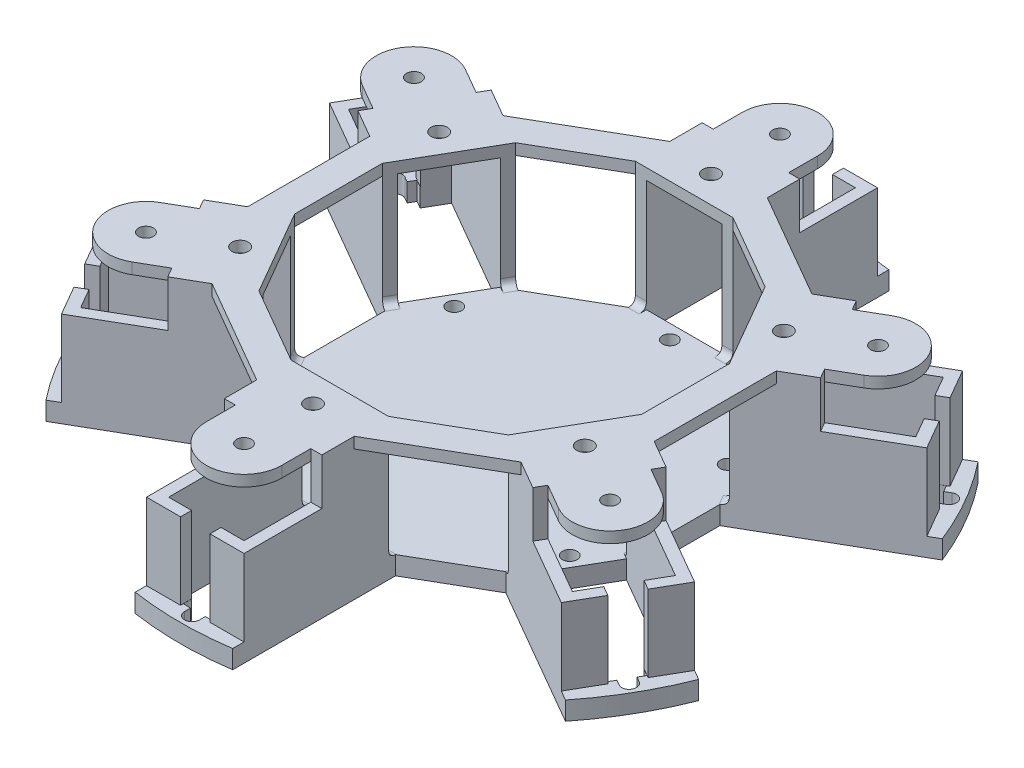
SolidWorks part; units mm, degrees
material "ABS"
ref_plane "Front" through (0, 0, 0) normal (0, 0, 1) x (1, 0, 0)
ref_plane "Top" through (0, 0, 0) normal (0, 1, 0) x (1, 0, 0)
ref_plane "Right" through (0, 0, 0) normal (1, 0, 0) x (0, 0, -1)
sketch "Sketch1" plane through (0, 0, 0) normal (0, 1, 0) x (1, 0, 0)
  line L0 (0, -57.15) -> (0, -56.41) construction
  line L1 (0, 57.15) -> (-49.4934, 28.575) construction
  line L2 (-49.4934, 28.575) -> (-49.4934, -28.575) construction
  line L3 (-49.4934, -28.575) -> (0, -57.15) construction
  line L4 (0, -57.15) -> (49.4934, -28.575) construction
  line L5 (49.4934, -28.575) -> (49.4934, 28.575) construction
  line L6 (49.4934, 28.575) -> (0, 57.15) construction
  line L7 (42.3635, 31.9642) -> (22.445, 20.4642)
  line L8 (-6.5, 52.67) -> (-2.5207, 52.67)
  line L9 (-6.5, 52.67) -> (-6.5, 29.67)
  line L10 (-6.5, 29.67) -> (6.5, 29.67)
  line L11 (6.5, 52.67) -> (6.5, 29.67)
  line L12 (-6.5, 52.67) -> (6.5, 29.67) construction
  line L13 (-6.5, 29.67) -> (6.5, 52.67) construction
  line L14 (42.3635, 31.9642) -> (44.3532, 28.518)
  line L15 (48.8635, 20.7058) -> (28.945, 9.2058)
  line L16 (22.445, 20.4642) -> (28.945, 9.2058)
  line L17 (48.8635, -20.7058) -> (28.945, -9.2058)
  line L18 (48.8635, -20.7058) -> (46.8739, -24.152)
  line L19 (42.3635, -31.9642) -> (22.445, -20.4642)
  line L20 (28.945, -9.2058) -> (22.445, -20.4642)
  line L21 (6.5, -52.67) -> (6.5, -29.67)
  line L22 (6.5, -52.67) -> (2.5207, -52.67)
  line L23 (-6.5, -52.67) -> (-6.5, -29.67)
  line L24 (6.5, -29.67) -> (-6.5, -29.67)
  line L25 (-42.3635, -31.9642) -> (-22.445, -20.4642)
  line L26 (-42.3635, -31.9642) -> (-44.3532, -28.518)
  line L27 (-48.8635, -20.7058) -> (-28.945, -9.2058)
  line L28 (-22.445, -20.4642) -> (-28.945, -9.2058)
  line L29 (-48.8635, 20.7058) -> (-28.945, 9.2058)
  line L30 (-48.8635, 20.7058) -> (-46.8739, 24.152)
  line L31 (-42.3635, 31.9642) -> (-22.445, 20.4642)
  line L32 (-28.945, 9.2058) -> (-22.445, 20.4642)
  line L33 (-1.27, 55.14) -> (-1.27, 54.1138)
  line L34 (-1.27, 54.1138) -> (-2.5207, 54.1138)
  line L35 (-2.5207, 54.1138) -> (-2.5207, 52.67)
  line L37 (2.5207, 54.1138) -> (2.5207, 52.67)
  line L38 (1.27, 54.1138) -> (2.5207, 54.1138)
  line L39 (1.27, 55.14) -> (1.27, 54.1138)
  line L40 (0, 53.87) -> (0, 57.15) construction
  line L41 (47.1176, 28.6698) -> (46.2289, 28.1567)
  line L42 (46.2289, 28.1567) -> (45.6035, 29.2399)
  line L43 (45.6035, 29.2399) -> (44.3532, 28.518)
  line L45 (48.1242, 24.8739) -> (46.8739, 24.152)
  line L46 (47.4989, 25.957) -> (48.1242, 24.8739)
  line L47 (48.3876, 26.4701) -> (47.4989, 25.957)
  line L48 (48.3876, -26.4701) -> (47.4989, -25.957)
  line L49 (47.4989, -25.957) -> (48.1242, -24.8739)
  line L50 (48.1242, -24.8739) -> (46.8739, -24.152)
  line L52 (45.6035, -29.2399) -> (44.3532, -28.518)
  line L53 (46.2289, -28.1567) -> (45.6035, -29.2399)
  line L54 (47.1176, -28.6698) -> (46.2289, -28.1567)
  line L55 (1.27, -55.14) -> (1.27, -54.1138)
  line L56 (1.27, -54.1138) -> (2.5207, -54.1138)
  line L57 (2.5207, -54.1138) -> (2.5207, -52.67)
  line L59 (-2.5207, -54.1138) -> (-2.5207, -52.67)
  line L60 (-1.27, -54.1138) -> (-2.5207, -54.1138)
  line L61 (-1.27, -55.14) -> (-1.27, -54.1138)
  line L62 (-47.1176, -28.6698) -> (-46.2289, -28.1567)
  line L63 (-46.2289, -28.1567) -> (-45.6035, -29.2399)
  line L64 (-45.6035, -29.2399) -> (-44.3532, -28.518)
  line L66 (-48.1242, -24.8739) -> (-46.8739, -24.152)
  line L67 (-47.4989, -25.957) -> (-48.1242, -24.8739)
  line L68 (-48.3876, -26.4701) -> (-47.4989, -25.957)
  line L69 (-48.3876, 26.4701) -> (-47.4989, 25.957)
  line L70 (-47.4989, 25.957) -> (-48.1242, 24.8739)
  line L71 (-48.1242, 24.8739) -> (-46.8739, 24.152)
  line L73 (-45.6035, 29.2399) -> (-44.3532, 28.518)
  line L74 (-46.2289, 28.1567) -> (-45.6035, 29.2399)
  line L75 (-47.1176, 28.6698) -> (-46.2289, 28.1567)
  line L76 (2.5207, 52.67) -> (6.5, 52.67)
  line L77 (-44.3532, 28.518) -> (-42.3635, 31.9642)
  line L78 (-46.8739, -24.152) -> (-48.8635, -20.7058)
  line L79 (0, -52.67) -> (0, 49.4934) construction
  line L80 (-2.5207, -52.67) -> (-6.5, -52.67)
  line L81 (44.3532, -28.518) -> (42.3635, -31.9642)
  line L82 (46.8739, 24.152) -> (48.8635, 20.7058)
  circle A0 centre (0, 0) radius 57.15
  circle A1 centre (0, 0) radius 49.4934 construction
  arc A2 (1.27, 55.14) -> (-1.27, 55.14) centre (0, 55.14) ccw
  circle A3 centre (0, 27.2) radius 1.27
  circle A5 centre (23.5559, 13.6) radius 1.27
  circle A7 centre (23.5559, -13.6) radius 1.27
  circle A9 centre (0, -27.2) radius 1.27
  circle A11 centre (-23.5559, -13.6) radius 1.27
  circle A13 centre (-23.5559, 13.6) radius 1.27
  circle A14 centre (-47.7526, 27.57) radius 1.27 [skipped]
  circle A15 centre (-47.7526, -27.57) radius 1.27 [skipped]
  circle A16 centre (0, -55.14) radius 1.27 [skipped]
  circle A17 centre (47.7526, -27.57) radius 1.27 [skipped]
  circle A18 centre (47.7526, 27.57) radius 1.27 [skipped]
  arc A19 (48.3876, 26.4701) -> (47.1176, 28.6698) centre (47.7526, 27.57) ccw
  arc A20 (47.1176, -28.6698) -> (48.3876, -26.4701) centre (47.7526, -27.57) ccw
  arc A21 (-1.27, -55.14) -> (1.27, -55.14) centre (0, -55.14) ccw
  arc A22 (-48.3876, -26.4701) -> (-47.1176, -28.6698) centre (-47.7526, -27.57) ccw
  arc A23 (-47.1176, 28.6698) -> (-48.3876, 26.4701) centre (-47.7526, 27.57) ccw
  point P3 (0, 41.17)
  point P11 (0, 0)
  point P13 (0, 0)
  point P14 (0, 0)
  point P64 (0, 0)
  point P69 (0, 52.67)
  point P120 (0, 0)
  dimension "D1" = 114.3
  dimension "D4" = 2.54
  dimension "D5" = 2.54
  dimension "D2" = 23
  dimension "D3" = 13
  dimension "D6" = 27.94
  dimension "D7" = 13.97
  dimension "D9" = 6
  dimension "D8" = 6
extrude "Boss-Extrude2" add sketch "Sketch1" along normal blind 3.175
sketch "Sketch2" plane through (0, 3.175, 0) normal (0, 1, 0) x (1, 0, 0)
  line L0 (0, 0) -> (-8.405, 56.5286) construction
  line L1 (0, 0) -> (-44.7527, 35.5432) construction
  line L2 (0, 0) -> (-25.4, 43.9941) construction
  line L3 (-44.7527, 35.5432) -> (-8.405, 56.5286) construction
  line L4 (-22.445, 20.4642) -> (-6.5, 29.67) construction
  line L6 (-8.405, 28.4804) -> (-20.4623, 21.5192)
  line L7 (-20.4623, 21.5192) -> (-44.7527, 35.5432)
  line L8 (-22.445, 20.4642) -> (-42.3635, 31.9642) construction
  line L9 (-8.405, 28.4804) -> (-8.405, 56.5286)
  line L25 (-6.5, 52.67) -> (-6.5, 29.67) construction
  line L26 (8.405, 28.4804) -> (8.405, 56.5286)
  line L27 (20.4623, 21.5192) -> (8.405, 28.4804)
  line L28 (20.4623, 21.5192) -> (44.7527, 35.5432)
  line L29 (28.8673, 6.9613) -> (53.1577, 20.9853)
  line L30 (28.8673, -6.9613) -> (28.8673, 6.9613)
  line L31 (28.8673, -6.9613) -> (53.1577, -20.9853)
  line L32 (20.4623, -21.5192) -> (44.7527, -35.5432)
  line L33 (8.405, -28.4804) -> (20.4623, -21.5192)
  line L34 (8.405, -28.4804) -> (8.405, -56.5286)
  line L35 (-8.405, -28.4804) -> (-8.405, -56.5286)
  line L36 (-20.4623, -21.5192) -> (-8.405, -28.4804)
  line L37 (-20.4623, -21.5192) -> (-44.7527, -35.5432)
  line L38 (-28.8673, -6.9613) -> (-53.1577, -20.9853)
  line L39 (-28.8673, 6.9613) -> (-28.8673, -6.9613)
  line L40 (-28.8673, 6.9613) -> (-53.1577, 20.9853)
  circle A0 centre (0, 0) radius 57.15 construction
  arc A1 (-8.405, 56.5286) -> (-44.7527, 35.5432) centre (0, 0) ccw
  arc A7 (44.7527, 35.5432) -> (8.405, 56.5286) centre (0, 0) ccw
  arc A8 (53.1577, -20.9853) -> (53.1577, 20.9853) centre (0, 0) ccw
  arc A9 (8.405, -56.5286) -> (44.7527, -35.5432) centre (0, 0) ccw
  arc A10 (-44.7527, -35.5432) -> (-8.405, -56.5286) centre (0, 0) ccw
  arc A11 (-53.1577, 20.9853) -> (-53.1577, -20.9853) centre (0, 0) ccw
  point P38 (0, 0)
  point P41 (0, 0)
  dimension "D1" = 1.905
  dimension "D2" = 6
extrude "Cut-Extrude1" cut sketch "Sketch2" against normal up to next
sketch "Sketch3" plane through (0, 3.175, 0) normal (0, 1, 0) x (1, 0, 0)
  line L0 (-6.5, 29.67) -> (6.5, 29.67) construction
  line L5 (42.3635, 31.9642) -> (22.445, 20.4642)
  line L6 (22.445, 20.4642) -> (21.4925, 22.1139)
  line L8 (-6.5, 52.67) -> (-6.5, 29.67)
  line L9 (-6.5, 29.67) -> (-8.405, 29.67)
  line L10 (-8.405, 52.67) -> (-8.405, 29.67)
  line L11 (0, 55.14) -> (0, 27.2146) construction
  line L12 (6.5, 29.67) -> (8.405, 29.67)
  line L13 (8.405, 52.67) -> (8.405, 29.67)
  line L15 (6.5, 52.67) -> (6.5, 29.67)
  line L57 (-8.405, 28.4804) -> (-8.405, 56.5286) construction
  line L58 (8.405, 56.5286) -> (8.405, 28.4804) construction
  line L59 (-6.5, 52.67) -> (6.5, 52.67)
  line L60 (-8.405, 52.67) -> (-8.405, 54.575)
  line L61 (-8.405, 54.575) -> (8.405, 54.575)
  line L62 (8.405, 52.67) -> (8.405, 54.575)
  line L63 (41.411, 33.6139) -> (21.4925, 22.1139)
  line L64 (28.945, 9.2058) -> (29.8975, 7.556)
  line L65 (49.816, 19.056) -> (29.8975, 7.556)
  line L66 (48.8635, 20.7058) -> (28.945, 9.2058)
  line L67 (42.3635, 31.9642) -> (48.8635, 20.7058)
  line L68 (41.411, 33.6139) -> (43.0608, 34.5664)
  line L69 (43.0608, 34.5664) -> (51.4658, 20.0085)
  line L70 (49.816, 19.056) -> (51.4658, 20.0085)
  line L71 (47.7526, 27.57) -> (23.5685, 13.6073) construction
  line L72 (48.8635, -20.7058) -> (28.945, -9.2058)
  line L73 (28.945, -9.2058) -> (29.8975, -7.556)
  line L74 (49.816, -19.056) -> (29.8975, -7.556)
  line L75 (22.445, -20.4642) -> (21.4925, -22.1139)
  line L76 (41.411, -33.6139) -> (21.4925, -22.1139)
  line L77 (42.3635, -31.9642) -> (22.445, -20.4642)
  line L78 (48.8635, -20.7058) -> (42.3635, -31.9642)
  line L79 (49.816, -19.056) -> (51.4658, -20.0085)
  line L80 (51.4658, -20.0085) -> (43.0608, -34.5664)
  line L81 (41.411, -33.6139) -> (43.0608, -34.5664)
  line L82 (47.7526, -27.57) -> (23.5685, -13.6073) construction
  line L83 (6.5, -52.67) -> (6.5, -29.67)
  line L84 (6.5, -29.67) -> (8.405, -29.67)
  line L85 (8.405, -52.67) -> (8.405, -29.67)
  line L86 (-6.5, -29.67) -> (-8.405, -29.67)
  line L87 (-8.405, -52.67) -> (-8.405, -29.67)
  line L88 (-6.5, -52.67) -> (-6.5, -29.67)
  line L89 (6.5, -52.67) -> (-6.5, -52.67)
  line L90 (8.405, -52.67) -> (8.405, -54.575)
  line L91 (8.405, -54.575) -> (-8.405, -54.575)
  line L92 (-8.405, -52.67) -> (-8.405, -54.575)
  line L93 (0, -55.14) -> (0, -27.2146) construction
  line L94 (-42.3635, -31.9642) -> (-22.445, -20.4642)
  line L95 (-22.445, -20.4642) -> (-21.4925, -22.1139)
  line L96 (-41.411, -33.6139) -> (-21.4925, -22.1139)
  line L97 (-28.945, -9.2058) -> (-29.8975, -7.556)
  line L98 (-49.816, -19.056) -> (-29.8975, -7.556)
  line L99 (-48.8635, -20.7058) -> (-28.945, -9.2058)
  line L100 (-42.3635, -31.9642) -> (-48.8635, -20.7058)
  line L101 (-41.411, -33.6139) -> (-43.0608, -34.5664)
  line L102 (-43.0608, -34.5664) -> (-51.4658, -20.0085)
  line L103 (-49.816, -19.056) -> (-51.4658, -20.0085)
  line L104 (-47.7526, -27.57) -> (-23.5685, -13.6073) construction
  line L105 (-48.8635, 20.7058) -> (-28.945, 9.2058)
  line L106 (-28.945, 9.2058) -> (-29.8975, 7.556)
  line L107 (-49.816, 19.056) -> (-29.8975, 7.556)
  line L108 (-22.445, 20.4642) -> (-21.4925, 22.1139)
  line L109 (-41.411, 33.6139) -> (-21.4925, 22.1139)
  line L110 (-42.3635, 31.9642) -> (-22.445, 20.4642)
  line L111 (-48.8635, 20.7058) -> (-42.3635, 31.9642)
  line L112 (-49.816, 19.056) -> (-51.4658, 20.0085)
  line L113 (-51.4658, 20.0085) -> (-43.0608, 34.5664)
  line L114 (-41.411, 33.6139) -> (-43.0608, 34.5664)
  line L115 (-47.7526, 27.57) -> (-23.5685, 13.6073) construction
  point P0 (0, 0)
  point P64 (0, 0)
  point P85 (0, 0)
  dimension "D1" = 6
  dimension "D2" = 1.905
extrude "Boss-Extrude3" add sketch "Sketch3" along normal blind 13.208
sketch "Sketch4" plane through (0, 0, -54.575) normal (0, 0, -1) x (-1, 0, 0)
  line L0 (0, 3.175) -> (0, 16.383) construction
  line L1 (8.405, 3.175) -> (-8.405, 3.175) construction
  line L2 (-8.405, 16.383) -> (8.405, 16.383) construction
  line L4 (-2.54, 16.383) -> (2.54, 16.383)
  line L5 (-2.54, 16.383) -> (-2.54, 3.175)
  line L6 (-2.54, 3.175) -> (2.54, 3.175)
  line L7 (2.54, 16.383) -> (2.54, 3.175)
  line L8 (-2.54, 16.383) -> (2.54, 3.175) construction
  line L9 (-2.54, 3.175) -> (2.54, 16.383) construction
  point P6 (0, 9.779)
  dimension "D1" = 5.08
extrude "Cut-Extrude2" cut sketch "Sketch4" against normal blind 13.208
ref_point "Point1"
pattern_circular "CirPattern2" count 6 every 60 about axis through (0, 3.175, 0) along (0, 1, 0) of "Cut-Extrude2"
fillet "Fillet1" radius 1.27 12 edges at (21.9687, 3.175, -21.289) (29.4212, 3.175, -8.3809) (29.4212, 3.175, 8.3809) (21.9687, 3.175, 21.289) (7.4525, 3.175, 29.67) (-7.4525, 3.175, 29.67) (-21.9687, 3.175, 21.289) (-29.4212, 3.175, 8.3809) (-29.4212, 3.175, -8.3809) (-21.9687, 3.175, -21.289) (-7.4525, 3.175, -29.67) (7.4525, 3.175, -29.67) conic rho 0.5
sketch "Sketch5" plane through (0, 16.383, 0) normal (0, 1, 0) x (1, 0, 0)
  line L0 (0, 52.67) -> (0, 29.67) construction
  line L2 (-6.5, 29.67) -> (6.5, 29.67) construction
  line L10 (-6.5, 29.67) -> (-6.5, 52.67) construction
  line L11 (-6.5, 41.17) -> (-8.405, 41.17)
  line L12 (-6.5, 41.17) -> (-6.5, 29.67)
  line L13 (-6.5, 29.67) -> (-8.405, 29.67)
  line L14 (-8.405, 41.17) -> (-8.405, 29.67)
  line L15 (-8.405, 29.67) -> (-6.5, 29.67) construction
  line L16 (-8.405, 54.575) -> (-8.405, 29.67) construction
  line L17 (6.5, 29.67) -> (8.405, 29.67)
  line L18 (8.405, 41.17) -> (8.405, 29.67)
  line L19 (6.5, 41.17) -> (8.405, 41.17)
  line L20 (6.5, 41.17) -> (6.5, 29.67)
  line L21 (32.4043, 26.2142) -> (22.445, 20.4642)
  line L22 (32.4043, 26.2142) -> (31.4518, 27.8639)
  line L23 (31.4518, 27.8639) -> (21.4925, 22.1139)
  line L24 (22.445, 20.4642) -> (21.4925, 22.1139)
  line L25 (28.945, 9.2058) -> (29.8975, 7.556)
  line L26 (39.8568, 13.306) -> (29.8975, 7.556)
  line L27 (38.9043, 14.9558) -> (39.8568, 13.306)
  line L28 (38.9043, 14.9558) -> (28.945, 9.2058)
  line L29 (38.9043, -14.9558) -> (28.945, -9.2058)
  line L30 (38.9043, -14.9558) -> (39.8568, -13.306)
  line L31 (39.8568, -13.306) -> (29.8975, -7.556)
  line L32 (28.945, -9.2058) -> (29.8975, -7.556)
  line L33 (22.445, -20.4642) -> (21.4925, -22.1139)
  line L34 (31.4518, -27.8639) -> (21.4925, -22.1139)
  line L35 (32.4043, -26.2142) -> (31.4518, -27.8639)
  line L36 (32.4043, -26.2142) -> (22.445, -20.4642)
  line L37 (6.5, -41.17) -> (6.5, -29.67)
  line L38 (6.5, -41.17) -> (8.405, -41.17)
  line L39 (8.405, -41.17) -> (8.405, -29.67)
  line L40 (6.5, -29.67) -> (8.405, -29.67)
  line L41 (-6.5, -29.67) -> (-8.405, -29.67)
  line L42 (-8.405, -41.17) -> (-8.405, -29.67)
  line L43 (-6.5, -41.17) -> (-8.405, -41.17)
  line L44 (-6.5, -41.17) -> (-6.5, -29.67)
  line L45 (-32.4043, -26.2142) -> (-22.445, -20.4642)
  line L46 (-32.4043, -26.2142) -> (-31.4518, -27.8639)
  line L47 (-31.4518, -27.8639) -> (-21.4925, -22.1139)
  line L48 (-22.445, -20.4642) -> (-21.4925, -22.1139)
  line L49 (-28.945, -9.2058) -> (-29.8975, -7.556)
  line L50 (-39.8568, -13.306) -> (-29.8975, -7.556)
  line L51 (-38.9043, -14.9558) -> (-39.8568, -13.306)
  line L52 (-38.9043, -14.9558) -> (-28.945, -9.2058)
  line L53 (-38.9043, 14.9558) -> (-28.945, 9.2058)
  line L54 (-38.9043, 14.9558) -> (-39.8568, 13.306)
  line L55 (-39.8568, 13.306) -> (-29.8975, 7.556)
  line L56 (-28.945, 9.2058) -> (-29.8975, 7.556)
  line L57 (-22.445, 20.4642) -> (-21.4925, 22.1139)
  line L58 (-31.4518, 27.8639) -> (-21.4925, 22.1139)
  line L59 (-32.4043, 26.2142) -> (-31.4518, 27.8639)
  line L60 (-32.4043, 26.2142) -> (-22.445, 20.4642)
  point P62 (0, 0)
  dimension "D1" = 6
extrude "Boss-Extrude4" add sketch "Sketch5" along normal blind 6.096
sketch "Sketch6" plane through (0, 22.479, 0) normal (0, 1, 0) x (1, 0, 0)
  line L0 (0, 52.67) -> (0, 29.67) construction
  line L1 (-2.54, 52.67) -> (-2.5207, 52.67) construction
  line L2 (-6.5, 29.67) -> (6.5, 29.67) construction
  line L3 (6.5, 52.67) -> (6.5, 41.17) construction
  line L4 (-20.3229, 21.5996) -> (-8.5443, 28.4) construction
  line L6 (-6.5, 46.17) -> (-6.5, 41.17)
  line L7 (-8.405, 41.17) -> (-6.5, 41.17)
  line L8 (-8.405, 41.17) -> (-8.405, 35.5878)
  line L9 (-8.405, 29.67) -> (8.405, 29.67)
  line L10 (8.405, 41.17) -> (8.405, 35.5878)
  line L11 (6.5, 46.17) -> (6.5, 41.17)
  line L12 (39.8568, 13.306) -> (35.0225, 10.515)
  line L13 (6.5, 41.17) -> (8.405, 41.17)
  line L14 (21.4925, 22.1139) -> (29.8975, 7.556)
  line L15 (31.4518, 27.8639) -> (26.6175, 25.0729)
  line L16 (31.4518, 27.8639) -> (32.4043, 26.2142)
  line L17 (36.7344, 28.7142) -> (32.4043, 26.2142)
  line L18 (43.2344, 17.4558) -> (38.9043, 14.9558)
  line L19 (38.9043, 14.9558) -> (39.8568, 13.306)
  line L20 (31.4518, -27.8639) -> (26.6175, -25.0729)
  line L21 (29.8975, -7.556) -> (21.4925, -22.1139)
  line L22 (39.8568, -13.306) -> (35.0225, -10.515)
  line L23 (39.8568, -13.306) -> (38.9043, -14.9558)
  line L24 (43.2344, -17.4558) -> (38.9043, -14.9558)
  line L25 (36.7344, -28.7142) -> (32.4043, -26.2142)
  line L26 (32.4043, -26.2142) -> (31.4518, -27.8639)
  line L27 (-8.405, -41.17) -> (-8.405, -35.5878)
  line L28 (8.405, -29.67) -> (-8.405, -29.67)
  line L29 (8.405, -41.17) -> (8.405, -35.5878)
  line L30 (8.405, -41.17) -> (6.5, -41.17)
  line L31 (6.5, -46.17) -> (6.5, -41.17)
  line L32 (-6.5, -46.17) -> (-6.5, -41.17)
  line L33 (-6.5, -41.17) -> (-8.405, -41.17)
  line L34 (-39.8568, -13.306) -> (-35.0225, -10.515)
  line L35 (-21.4925, -22.1139) -> (-29.8975, -7.556)
  line L36 (-31.4518, -27.8639) -> (-26.6175, -25.0729)
  line L37 (-31.4518, -27.8639) -> (-32.4043, -26.2142)
  line L38 (-36.7344, -28.7142) -> (-32.4043, -26.2142)
  line L39 (-43.2344, -17.4558) -> (-38.9043, -14.9558)
  line L40 (-38.9043, -14.9558) -> (-39.8568, -13.306)
  line L41 (-31.4518, 27.8639) -> (-26.6175, 25.0729)
  line L42 (-29.8975, 7.556) -> (-21.4925, 22.1139)
  line L43 (-39.8568, 13.306) -> (-35.0225, 10.515)
  line L44 (-39.8568, 13.306) -> (-38.9043, 14.9558)
  line L45 (-43.2344, 17.4558) -> (-38.9043, 14.9558)
  line L46 (-36.7344, 28.7142) -> (-32.4043, 26.2142)
  line L47 (-32.4043, 26.2142) -> (-31.4518, 27.8639)
  line L48 (-8.405, 29.67) -> (-21.4925, 22.1139)
  line L49 (-8.405, 35.5878) -> (-26.6175, 25.0729)
  line L50 (26.6175, 25.0729) -> (8.405, 35.5878)
  line L51 (21.4925, 22.1139) -> (8.405, 29.67)
  line L52 (35.0225, -10.515) -> (35.0225, 10.515)
  line L53 (29.8975, -7.556) -> (29.8975, 7.556)
  line L54 (8.405, -35.5878) -> (26.6175, -25.0729)
  line L55 (8.405, -29.67) -> (21.4925, -22.1139)
  line L56 (-26.6175, -25.0729) -> (-8.405, -35.5878)
  line L57 (-21.4925, -22.1139) -> (-8.405, -29.67)
  line L58 (-35.0225, 10.515) -> (-35.0225, -10.515)
  line L59 (-29.8975, 7.556) -> (-29.8975, -7.556)
  circle A0 centre (0, 46.17) radius 6.5 construction
  arc A1 (-6.5, 46.17) -> (6.5, 46.17) centre (0, 46.17) cw
  arc A2 (36.7344, 28.7142) -> (43.2344, 17.4558) centre (39.9844, 23.085) cw
  arc A3 (43.2344, -17.4558) -> (36.7344, -28.7142) centre (39.9844, -23.085) cw
  arc A4 (6.5, -46.17) -> (-6.5, -46.17) centre (0, -46.17) cw
  arc A5 (-36.7344, -28.7142) -> (-43.2344, -17.4558) centre (-39.9844, -23.085) cw
  arc A6 (-43.2344, 17.4558) -> (-36.7344, 28.7142) centre (-39.9844, 23.085) cw
  point P70 (0, 0)
  point P92 (0, 0)
  dimension "D1" = 6
  dimension "D3" = 6
extrude "Boss-Extrude5" add sketch "Sketch6" along normal blind 1.905
sketch "Sketch7" plane through (0, 24.384, 0) normal (0, 1, 0) x (1, 0, 0)
  line L0 (-6.5, 46.17) -> (6.5, 46.17) construction
  circle A0 centre (0, 46.17) radius 1.27
  circle A1 centre (39.9844, 23.085) radius 1.27
  circle A2 centre (39.9844, -23.085) radius 1.27
  circle A3 centre (0, -46.17) radius 1.27
  circle A4 centre (-39.9844, -23.085) radius 1.27
  circle A5 centre (-39.9844, 23.085) radius 1.27
  point P6 (0, 0)
  point P18 (0, 0)
  dimension "D1" = 2.54
  dimension "D2" = 6
extrude "Cut-Extrude3" cut sketch "Sketch7" against normal up to next
sketch "Sketch8" plane through (0, 0, 0) normal (0, -1, 0) x (1, 0, 0)
  line L0 (-8.405, 28.4804) -> (-8.405, 56.5286) construction
  line L1 (-6.5, 29.67) -> (-8.405, 29.67)
  line L2 (-6.5, 29.67) -> (-6.5, 52.67)
  line L3 (-6.5, 52.67) -> (-8.405, 52.67)
  line L4 (-8.405, 29.67) -> (-8.405, 52.67)
  line L5 (0, 55.14) -> (0, 27.2) construction
  line L6 (-6.5, 52.67) -> (-2.5207, 52.67) construction
  line L7 (6.5, 52.67) -> (8.405, 52.67)
  line L8 (8.405, 29.67) -> (8.405, 52.67)
  line L9 (6.5, 29.67) -> (8.405, 29.67)
  line L10 (6.5, 29.67) -> (6.5, 52.67)
  line L12 (48.8635, 20.7058) -> (49.816, 19.056)
  line L13 (29.8975, 7.556) -> (49.816, 19.056)
  line L14 (28.945, 9.2058) -> (29.8975, 7.556)
  line L15 (28.945, 9.2058) -> (48.8635, 20.7058)
  line L16 (22.445, 20.4642) -> (42.3635, 31.9642)
  line L17 (22.445, 20.4642) -> (21.4925, 22.1139)
  line L18 (21.4925, 22.1139) -> (41.411, 33.6139)
  line L19 (42.3635, 31.9642) -> (41.411, 33.6139)
  line L20 (42.3635, -31.9642) -> (41.411, -33.6139)
  line L21 (21.4925, -22.1139) -> (41.411, -33.6139)
  line L22 (22.445, -20.4642) -> (21.4925, -22.1139)
  line L23 (22.445, -20.4642) -> (42.3635, -31.9642)
  line L24 (28.945, -9.2058) -> (48.8635, -20.7058)
  line L25 (28.945, -9.2058) -> (29.8975, -7.556)
  line L26 (29.8975, -7.556) -> (49.816, -19.056)
  line L27 (48.8635, -20.7058) -> (49.816, -19.056)
  line L28 (-6.5, -52.67) -> (-8.405, -52.67)
  line L29 (-8.405, -29.67) -> (-8.405, -52.67)
  line L30 (-6.5, -29.67) -> (-8.405, -29.67)
  line L31 (-6.5, -29.67) -> (-6.5, -52.67)
  line L32 (6.5, -29.67) -> (6.5, -52.67)
  line L33 (6.5, -29.67) -> (8.405, -29.67)
  line L34 (8.405, -29.67) -> (8.405, -52.67)
  line L35 (6.5, -52.67) -> (8.405, -52.67)
  line L36 (-48.8635, -20.7058) -> (-49.816, -19.056)
  line L37 (-29.8975, -7.556) -> (-49.816, -19.056)
  line L38 (-28.945, -9.2058) -> (-29.8975, -7.556)
  line L39 (-28.945, -9.2058) -> (-48.8635, -20.7058)
  line L40 (-22.445, -20.4642) -> (-42.3635, -31.9642)
  line L41 (-22.445, -20.4642) -> (-21.4925, -22.1139)
  line L42 (-21.4925, -22.1139) -> (-41.411, -33.6139)
  line L43 (-42.3635, -31.9642) -> (-41.411, -33.6139)
  line L44 (-42.3635, 31.9642) -> (-41.411, 33.6139)
  line L45 (-21.4925, 22.1139) -> (-41.411, 33.6139)
  line L46 (-22.445, 20.4642) -> (-21.4925, 22.1139)
  line L47 (-22.445, 20.4642) -> (-42.3635, 31.9642)
  line L48 (-28.945, 9.2058) -> (-48.8635, 20.7058)
  line L49 (-28.945, 9.2058) -> (-29.8975, 7.556)
  line L50 (-29.8975, 7.556) -> (-49.816, 19.056)
  line L51 (-48.8635, 20.7058) -> (-49.816, 19.056)
  point P59 (0, 0)
  dimension "D1" = 6
extrude "Boss-Extrude6" [suppressed] add sketch "Sketch8" along normal blind 6.35
sketch "Sketch9" plane through (0, 0, 0) normal (0, -1, 0) x (1, 0, 0)
  line L0 (8.405, -28.4804) -> (-8.405, -28.4804)
  line L1 (-8.405, 24.9687) -> (8.405, 24.9687)
  line L2 (8.405, 24.9687) -> (8.405, 35.0925)
  line L3 (8.405, 56.5286) -> (8.405, 28.4804) construction
  line L4 (8.405, 35.0925) -> (44.2076, 42.1004)
  line L5 (44.2076, 42.1004) -> (56.6527, 22.889)
  line L6 (56.6527, 22.889) -> (57.2815, -47.068)
  line L7 (57.2815, -47.068) -> (-16.4259, -92.7274)
  line L8 (-16.4259, -92.7274) -> (-91.3916, -39.5846)
  line L9 (-91.3916, -39.5846) -> (-78.4595, 36.5934)
  line L10 (-78.4595, 36.5934) -> (-30.3683, 56.5286)
  line L11 (-30.3683, 56.5286) -> (-8.405, 35.0925)
  line L12 (-8.405, 28.4804) -> (-8.405, 56.5286) construction
  line L13 (-8.405, 35.0925) -> (-8.405, 24.9687)
extrude "Cut-Extrude5" [suppressed] cut sketch "Sketch9" against normal through all
sketch "Sketch10" plane through (0, 24.384, 0) normal (0, 1, 0) x (1, 0, 0)
  line L0 (0, 0) -> (0, 34.29) construction
  circle A0 centre (0, 34.29) radius 1.397
  circle A1 centre (29.696, 17.145) radius 1.397
  circle A2 centre (29.696, -17.145) radius 1.397
  circle A3 centre (0, -34.29) radius 1.397
  circle A4 centre (-29.696, -17.145) radius 1.397
  circle A5 centre (-29.696, 17.145) radius 1.397
  point P16 (0, 0)
  dimension "D1" = 2.794
  dimension "D3" = 34.29
  dimension "D2" = 6
extrude "Cut-Extrude6" cut sketch "Sketch10" against normal up to next
